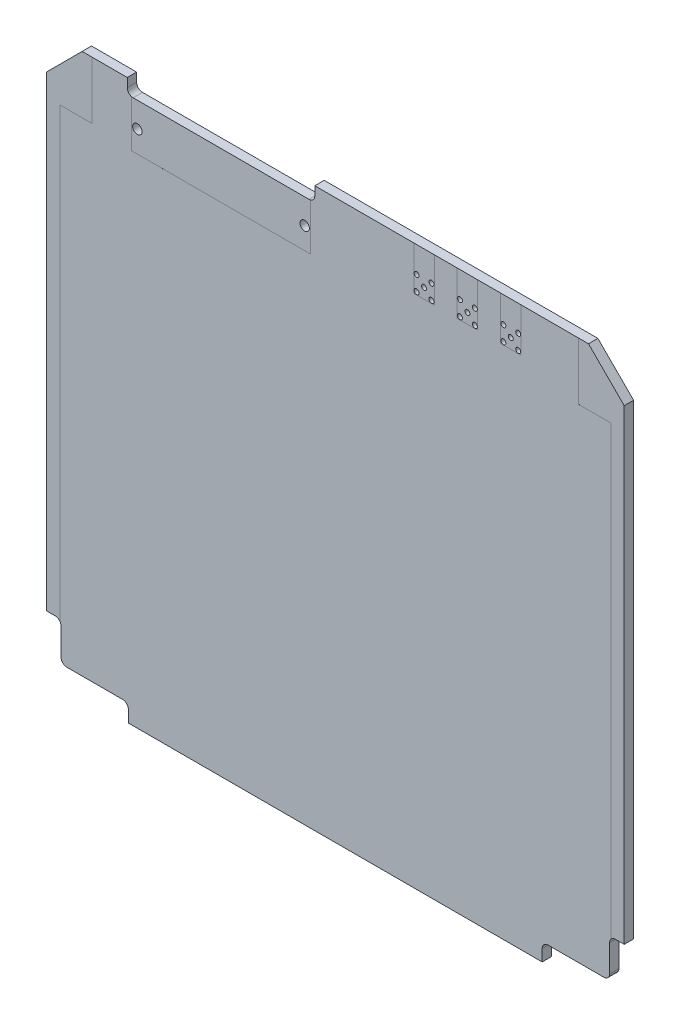
SolidWorks part; units mm, degrees
ref_plane "Front Plane" through (0, 0, 0) normal (0, 0, 1) x (1, 0, 0)
ref_plane "Top Plane" through (0, 0, 0) normal (0, 1, 0) x (1, 0, 0)
ref_plane "Right Plane" through (0, 0, 0) normal (1, 0, 0) x (0, 0, -1)
ref_plane "Plane4" through (0, 0, -0.0125) normal (0, 0, -1) x (-1, 0, 0)
sketch "Sketch1" plane through (0, 0, -0.0125) normal (0, 0, -1) x (-1, 0, 0)
  line L0 (35.3, -50) -> (35.3, -48)
  line L1 (36.3, -47) -> (45.8, -47)
  line L2 (46.8, -46) -> (46.8, -41.4)
  line L3 (47.8, -40.4) -> (49.3, -40.4)
  line L4 (49.3, -40.4) -> (49.3, 39.2)
  line L5 (49.3, 39.2) -> (43.2, 45.3)
  line L6 (43.2, 45.3) -> (35.5, 45.3)
  line L7 (35.5, 45.3) -> (35.5, 43.8)
  line L8 (34.5, 42.8) -> (4.5, 42.8)
  line L9 (3.5, 43.8) -> (3.5, 45.3)
  line L10 (3.5, 45.3) -> (-43.2, 45.3)
  line L11 (-43.2, 45.3) -> (-49.3, 39.2)
  line L12 (-49.3, 39.2) -> (-49.3, -40.4)
  line L13 (-49.3, -40.4) -> (-47.8, -40.4)
  line L14 (-46.8, -41.4) -> (-46.8, -46)
  line L15 (-45.8, -47) -> (-36.3, -47)
  line L16 (-35.3, -48) -> (-35.3, -50)
  line L17 (-35.3, -50) -> (35.3, -50)
  line L18 (0, -50) -> (0, 45.3) construction
  line L19 (19.5, 42.8) -> (19.5, 25.5258) construction
  line L20 (-13.87, 40.87) -> (-16.41, 38.33) construction
  line L21 (-21.27, 40.87) -> (-23.81, 38.33) construction
  line L22 (-28.67, 40.87) -> (-31.21, 38.33) construction
  arc A0 (35.3, -48) -> (36.3, -47) centre (36.3, -48) cw
  arc A1 (45.8, -47) -> (46.8, -46) centre (45.8, -46) ccw
  arc A2 (46.8, -41.4) -> (47.8, -40.4) centre (47.8, -41.4) cw
  arc A3 (35.5, 43.8) -> (34.5, 42.8) centre (34.5, 43.8) cw
  arc A4 (4.5, 42.8) -> (3.5, 43.8) centre (4.5, 43.8) cw
  arc A5 (-47.8, -40.4) -> (-46.8, -41.4) centre (-47.8, -41.4) cw
  arc A6 (-46.8, -46) -> (-45.8, -47) centre (-45.8, -46) ccw
  arc A7 (-36.3, -47) -> (-35.3, -48) centre (-36.3, -48) cw
  circle A8 centre (-21.27, 40.87) radius 0.425
  circle A9 centre (-23.81, 40.87) radius 0.425
  circle A10 centre (-22.54, 39.6) radius 0.425
  circle A11 centre (-13.87, 40.87) radius 0.425
  circle A12 centre (-23.81, 38.33) radius 0.425
  circle A13 centre (-16.41, 40.87) radius 0.425
  circle A14 centre (-15.14, 39.6) radius 0.425
  circle A15 centre (-21.27, 38.33) radius 0.425
  circle A16 centre (-28.67, 40.87) radius 0.425
  circle A17 centre (-31.21, 40.87) radius 0.425
  circle A18 centre (-16.41, 38.33) radius 0.425
  circle A19 centre (-29.94, 39.6) radius 0.425
  circle A20 centre (-31.21, 38.33) radius 0.425
  circle A21 centre (-28.67, 38.33) radius 0.425
  circle A22 centre (33.775, 38.54) radius 0.8
  circle A23 centre (5.225, 38.54) radius 0.8
  circle A24 centre (-13.87, 38.33) radius 0.425
  point P35 (-15.14, 39.6)
  dimension "D7" = 2.5
  dimension "D8" = 1.6
  dimension "D9" = 14.275
  dimension "D10" = 4.26
  dimension "D11" = 1
  dimension "D12" = 1
  dimension "D13" = 1
  dimension "D14" = 1
  dimension "D15" = 1
  dimension "D16" = 1
  dimension "D17" = 1
  dimension "D18" = 1
  dimension "D26" = 0.85
  dimension "D1" = 98.6
  dimension "D2" = 95.3
  dimension "D3" = 14
  dimension "D4" = 9.6
  dimension "D5" = 2.5
  dimension "D6" = 3
  dimension "D19" = 14
  dimension "D20" = 2.5
  dimension "D21" = 6.1
  dimension "D22" = 6.1
  dimension "D23" = 32
  dimension "D24" = 2.54
  dimension "D25" = 2.54
  dimension "D28" = 7.4
  dimension "D29" = 4.43
  dimension "D30" = 35.43
  dimension "D31" = 45
  dimension "D32" = 45
  dimension "D33" = 29.8
  dimension "D34" = 50
  dimension "D27" = 3
extrude "Boss-Extrude1" add sketch "Sketch1" against normal blind 1.6
sketch "thermalContacts_lower" plane through (0, 0, -0.0125) normal (0, 0, -1) x (-1, 0, 0)
  line L0 (47, 35.5) -> (47, -41.5) construction
  line L1 (41.5, 35.5) -> (41.5, 41.5) construction
  line L2 (41.5, 35.5) -> (47, 35.5) construction
  line L3 (47, 35.5) -> (47, -41.5)
  line L4 (41.5, 35.5) -> (41.5, 41.5)
  line L5 (41.5, 35.5) -> (47, 35.5)
  line L6 (-47, 35.5) -> (-47, -41.5) construction
  line L7 (-41.5, 35.5) -> (-47, 35.5) construction
  line L8 (-41.5, 35.5) -> (-41.5, 41.5) construction
  line L9 (-47, 35.5) -> (-47, -41.5)
  line L10 (-41.5, 35.5) -> (-47, 35.5)
  line L11 (-41.5, 35.5) -> (-41.5, 41.5)
  line L12 (-41.5, 41.5) -> (-41.5, 47) construction
  line L13 (-41.5, 41.5) -> (-49.5, 41.5) construction
  line L14 (-41.5, 41.5) -> (-41.5, 47)
  line L15 (-41.5, 41.5) -> (-49.5, 41.5) construction
  line L16 (41.5, 41.5) -> (41.5, 47) construction
  line L17 (41.5, 41.5) -> (49.5, 41.5) construction
  line L18 (41.5, 41.5) -> (41.5, 47)
  line L19 (41.5, 41.5) -> (49.5, 41.5) construction
  line L20 (-47, -41.5) -> (59.8273, -41.5)
  line L21 (59.8273, -41.5) -> (59.8273, 47)
  line L22 (59.8273, 47) -> (-41.5, 47)
  line L23 (41.5, 47) -> (-56.1922, 47)
  line L24 (-56.1922, 47) -> (-56.1922, -41.5)
  line L25 (-56.1922, -41.5) -> (47, -41.5)
sketch "thermalContacts_upper" plane through (0, 0, 1.5875) normal (0, 0, 1) x (1, 0, 0)
  line L3 (-47, 35.5) -> (-47, -41.5)
  line L4 (-41.5, 35.5) -> (-41.5, 41.5)
  line L5 (-41.5, 35.5) -> (-47, 35.5)
  line L9 (47, 35.5) -> (47, -41.5)
  line L10 (41.5, 35.5) -> (47, 35.5)
  line L11 (41.5, 35.5) -> (41.5, 41.5)
  line L14 (41.5, 41.5) -> (41.5, 47)
  line L15 (41.5, 41.5) -> (49.5, 41.5) construction
  line L18 (-41.5, 41.5) -> (-41.5, 47)
  line L19 (-41.5, 41.5) -> (-49.5, 41.5) construction
  line L20 (47, -41.5) -> (59.8273, -41.5)
  line L21 (59.8273, -41.5) -> (59.8273, 47)
  line L22 (59.8273, 47) -> (41.5, 47)
  line L23 (-41.5, 47) -> (-56.1922, 47)
  line L24 (-56.1922, 47) -> (-56.1922, -41.5)
  line L25 (-56.1922, -41.5) -> (-47, -41.5)
extrude "Cut-Extrude1" cut sketch "thermalContacts_lower" against normal blind 0.0001 rebuild error yes
extrude "Cut-Extrude2" cut sketch "thermalContacts_upper" against normal blind 0.0001
sketch "partFootprints" plane through (0, 0, 1.5875) normal (0, 0, 1) x (1, 0, 0)
  line L0 (-34.74, 34.84) -> (-34.74, 42.8292)
  line L1 (-4.26, 34.84) -> (-34.74, 34.84)
  line L2 (-41.5, 45.3) -> (-35.5, 45.3) construction
  line L3 (-36.1132, 45.3) -> (-39.5054, 45.3) construction
  line L4 (-4.26, 34.84) -> (-4.26, 42.8292)
  line L5 (-49.3, -40.4) -> (-49.3, 39.2) construction
  line L6 (13.39, 45.3) -> (13.39, 37.85)
  line L7 (13.39, 37.85) -> (16.89, 37.85)
  line L8 (16.89, 37.85) -> (16.89, 45.3)
  line L9 (16.89, 45.3) -> (13.39, 45.3)
  line L10 (20.79, 45.3) -> (20.79, 37.85)
  line L11 (20.79, 37.85) -> (24.29, 37.85)
  line L12 (24.29, 37.85) -> (24.29, 45.3)
  line L13 (24.29, 45.3) -> (20.79, 45.3)
  line L14 (28.19, 45.3) -> (28.19, 37.85)
  line L15 (28.19, 37.85) -> (31.69, 37.85)
  line L16 (31.69, 37.85) -> (31.69, 45.3)
  line L17 (31.69, 45.3) -> (28.19, 45.3)
  line L18 (49.3, -40.4) -> (49.3, 39.2) construction
  line L20 (-34.74, 42.8292) -> (-4.26, 42.8292)
  line L21 (-3.5, 45.3) -> (41.5, 45.3) construction
  arc A0 (-35.5, 43.8) -> (-34.5, 42.8) centre (-34.5, 43.8) ccw construction
  arc A1 (-4.5, 42.8) -> (-3.5, 43.8) centre (-4.5, 43.8) ccw construction
  dimension "D1" = 10.46
  dimension "D2" = 14.56
  dimension "D3" = 30.48
  dimension "D4" = 3.5
  dimension "D5" = 7.45
  dimension "D7" = 7.4
  dimension "D8" = 17.61
  dimension "D6" = 3
extrude "Cut-Extrude3" cut sketch "partFootprints" against normal blind 0.0001
